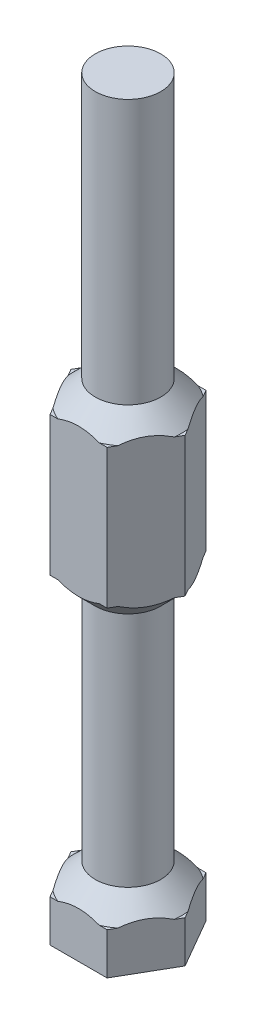
SolidWorks part; units mm, degrees
ref_plane "Front Plane" through (0, 0, 0) normal (0, 0, 1) x (1, 0, 0)
ref_plane "Top Plane" through (0, 0, 0) normal (0, 1, 0) x (1, 0, 0)
ref_plane "Right Plane" through (0, 0, 0) normal (1, 0, 0) x (0, 0, -1)
sketch "Sketch1" plane through (0, 0, 0) normal (0, 1, 0) x (1, 0, 0)
  line L1 (2.0496, -3.55) -> (4.0992, 0)
  line L2 (4.0992, 0) -> (2.0496, 3.55)
  line L3 (2.0496, 3.55) -> (-2.0496, 3.55)
  line L4 (-2.0496, 3.55) -> (-4.0992, 0)
  line L5 (-4.0992, 0) -> (-2.0496, -3.55)
  line L6 (-2.0496, -3.55) -> (2.0496, -3.55)
  circle A0 centre (0, 0) radius 3.55 construction
  dimension "D1" = 7.1
extrude "Boss-Extrude1" add sketch "Sketch1" along normal blind 3
sketch "Sketch2" plane through (0, 3, 0) normal (0, 1, 0) x (1, 0, 0)
  circle A0 centre (0, 0) radius 2.35
  dimension "D1" = 4.7
extrude "Boss-Extrude2" add sketch "Sketch2" along normal blind 20
extrude "Boss-Extrude3" add sketch "Sketch1<2>" along normal blind 10 from surface starting at face at (0, 23, 2.35)
sketch "Sketch1<2>" plane through (0, 0, 0) normal (0, 1, 0) x (1, 0, 0) same geometry as "Sketch1"
extrude "Boss-Extrude4" add sketch "Sketch2<2>" along normal blind 20.5 from surface starting at face at (0, 33, 0)
sketch "Sketch2<2>" plane through (0, 3, 0) normal (0, 1, 0) x (1, 0, 0) same geometry as "Sketch2"
chamfer "Chamfer1" distance 1.5 angle 45 3 edges at (0, 23, 2.35) (0, 3, 2.35) (0, 33, -2.35)
